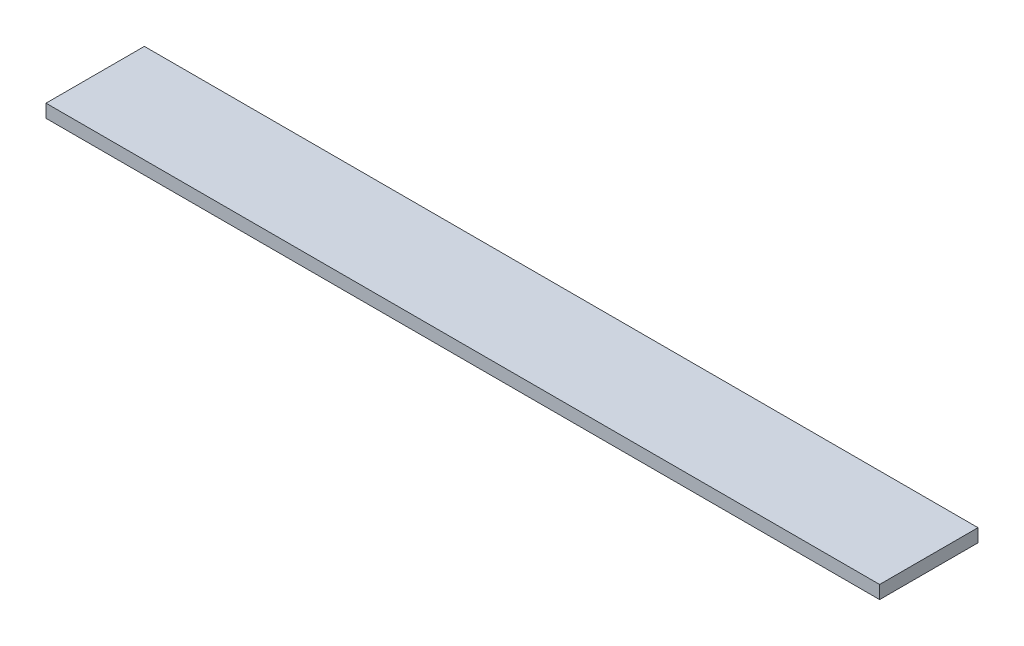
SolidWorks part; units mm, degrees
material "Oak"
ref_plane "Front Plane" through (0, 0, 0) normal (0, 0, 1) x (1, 0, 0)
ref_plane "Top Plane" through (0, 0, 0) normal (0, 1, 0) x (1, 0, 0)
ref_plane "Right Plane" through (0, 0, 0) normal (1, 0, 0) x (0, 0, -1)
sketch "Sketch1" plane through (0, 0, 0) normal (0, 1, 0) x (1, 0, 0)
  line L1 (0, 0) -> (805, 0)
  line L2 (0, 0) -> (0, 95)
  line L3 (0, 95) -> (805, 95)
  line L4 (805, 0) -> (805, 95)
  dimension "D1" = 95
  dimension "D2" = 805
extrude "Boss-Extrude1" add sketch "Sketch1" along normal blind 12.7
